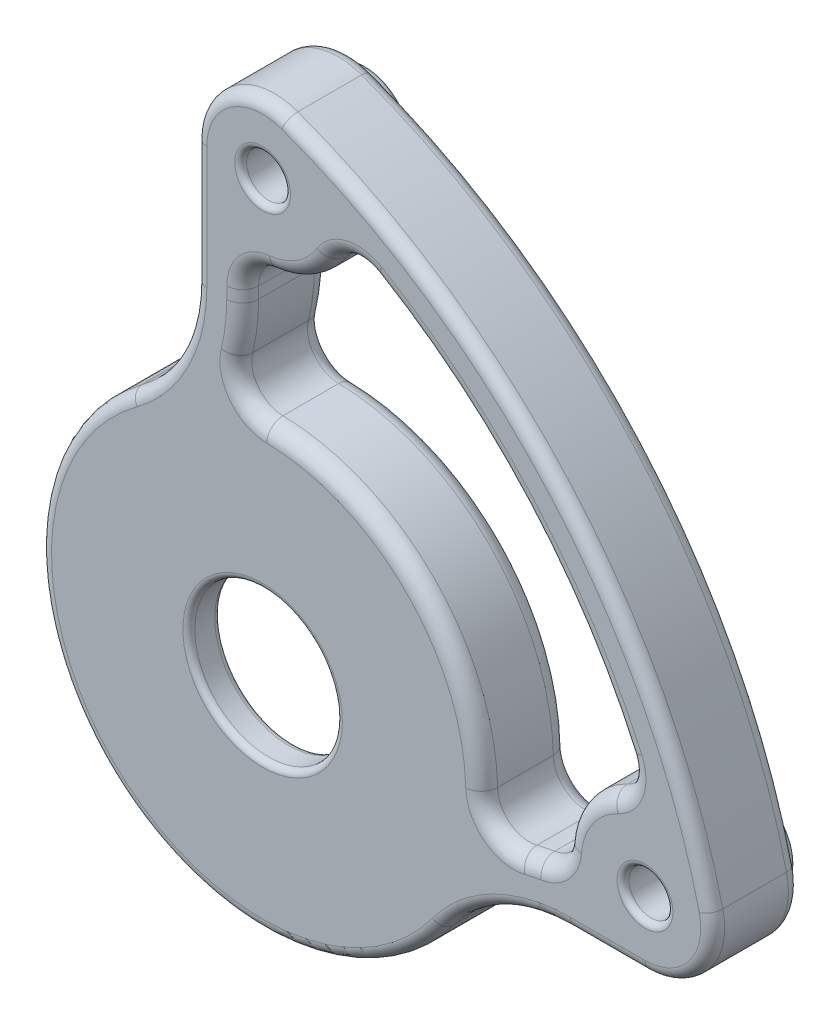
SolidWorks part; units mm, degrees
ref_plane "Front Plane" through (0, 0, 0) normal (0, 0, 1) x (1, 0, 0)
ref_plane "Top Plane" through (0, 0, 0) normal (0, 1, 0) x (1, 0, 0)
ref_plane "Right Plane" through (0, 0, 0) normal (1, 0, 0) x (0, 0, -1)
sketch "Sketch1" plane through (0, 0, 0) normal (0, 0, 1) x (1, 0, 0)
  line L0 (-4.25, 27) -> (-4.25, 19.3116)
  line L1 (24, -4.25) -> (19.3116, -4.25)
  circle A0 centre (0, 0) radius 4.63
  arc A1 (-8.3125, 11.2651) -> (11.2651, -8.3125) centre (0, 0) ccw
  circle A2 centre (0, 27) radius 1.375
  circle A3 centre (24, 0) radius 1.375
  arc A4 (1.4667, 30.9889) -> (-4.25, 27) centre (0, 27) ccw
  arc A5 (24, -4.25) -> (28.1333, 0.9889) centre (24, 0) ccw
  arc A6 (28.1333, 0.9889) -> (1.4667, 30.9889) centre (-13.2001, -8.9001) ccw
  arc A7 (19.3116, -4.25) -> (11.2651, -8.3125) centre (19.3116, -14.25) ccw
  arc A8 (-4.25, 19.3116) -> (-8.3125, 11.2651) centre (-14.25, 19.3116) cw
  dimension "D1" = 9.26
  dimension "D2" = 28
  dimension "D3" = 2.75
  dimension "D6" = 8.5
  dimension "D7" = 8.5
  dimension "D8" = 85
  dimension "D9" = 10
  dimension "D4" = 27
  dimension "D5" = 24
extrude "Boss-Extrude1" add sketch "Sketch1" along normal blind 5.5
sketch "Sketch2" plane through (0, 0, 5.5) normal (0, 0, 1) x (1, 0, 0)
  circle A0 centre (0, 27) radius 3
  circle A1 centre (24, 0) radius 3
  circle A2 centre (24, 0) radius 1.375 construction
  circle A3 centre (0, 27) radius 1.375 construction
  circle A4 centre (24, 0) radius 1.375
  circle A5 centre (0, 27) radius 1.375
  dimension "D1" = 6
extrude "Boss-Extrude2" add sketch "Sketch2" along normal blind 1
sketch "Sketch3" plane through (0, 0, 5.5) normal (0, 0, 1) x (1, 0, 0)
  line L2 (-1.25, 19.3116) -> (-1.25, 27)
  line L3 (-1.25, 19.3116) -> (-1.25, 22.1588)
  line L4 (24, -1.25) -> (19.3116, -1.25)
  circle A0 centre (0, 0) radius 11.75
  arc A3 (19.3116, -1.25) -> (8.8511, -6.5313) centre (19.3116, -14.25) ccw
  arc A4 (25.2157, 0.2909) -> (0.4314, 28.1732) centre (-13.2001, -8.9001) ccw
  arc A5 (23.7752, 4.9949) -> (4.9341, 26.1912) centre (-13.2001, -8.9001) ccw
  arc A6 (19.159, -1.2509) -> (13.4976, -2.6226) centre (19.3116, -14.25) ccw
  arc A7 (-6.5312, 8.8511) -> (-1.25, 19.3116) centre (-14.25, 19.3116) ccw
  arc A8 (-2.6226, 13.4976) -> (-1.25, 19.3116) centre (-14.25, 19.3116) ccw
  circle A10 centre (24, 0) radius 5
  arc A11 (23.7752, 4.9949) -> (19.159, -1.2509) centre (24, 0) ccw
  circle A13 centre (0, 27) radius 5
  arc A14 (-1.25, 22.1588) -> (4.9341, 26.1912) centre (0, 27) ccw
  arc A15 (13.4976, -2.6226) -> (-2.6226, 13.4976) centre (0, 0) ccw
  circle A18 centre (0, 0) radius 13.75 construction
  circle M16 centre (0, 0) radius 4.63
  dimension "D1" = 23.5
  dimension "D2" = 3
  dimension "D3" = 3
  dimension "D4" = 2
  dimension "D5" = 2
  dimension "D6" = 3
  dimension "D7" = 2
extrude "Cut-Extrude1" cut sketch "Sketch3" against normal blind 3.5 contours A0 M16 region at (6.4231, 9.4396, 5.5)
extrude "Cut-Extrude2" cut sketch "Sketch3<3>" against normal through all contours A15 A11 A5 A14 L3 A8 region at (11.2082, 13.0572, 5.5)
sketch "Sketch3<3>" plane through (0, 0, 5.5) normal (0, 0, 1) x (1, 0, 0) same geometry as "Sketch3"
fillet "Fillet1" radius 2 6 edges at (23.7752, 4.9949, 2.75) (4.9341, 26.1912, 2.75) (-1.25, 22.1588, 2.75) (-2.6226, 13.4976, 2.75) (19.159, -1.2509, 2.75) (13.4976, -2.6226, 2.75)
fillet "Fillet2" radius 1 26 edges at (-0.738, 21.3766, 0) (-1.2655, 14.528, 0) (9.7227, 9.7227, 0) (19.9006, 2.8627, 0) (22.9306, 5.6489, 0) (16.3225, 17.3422, 0) (5.4846, 25.2756, 0) (-0.738, 21.3766, 5.5) (-1.2655, 14.528, 5.5) (9.7227, 9.7227, 5.5) (19.9006, 2.8627, 5.5) (22.9306, 5.6489, 5.5) (16.3225, 17.3422, 5.5) (5.4846, 25.2756, 5.5) (2.6705, 22.7729, 0) (2.6705, 22.7729, 5.5) (-1.3435, 17.7556, 0) (-1.3435, 17.7556, 5.5) (-1.25, 19.6759, 0) (-1.25, 19.6759, 5.5) (14.528, -1.2655, 0) (16.773, -1.5003, 0) (18.4871, -0.7887, 0) (14.528, -1.2655, 5.5) (16.773, -1.5003, 5.5) (18.4871, -0.7887, 5.5)
fillet "Fillet3" radius 0.75 16 edges at (27.3366, -2.6325, 0) (21.6558, -4.25, 0) (14.8047, -5.3232, 0) (-9.8995, -9.8995, 0) (-5.3232, 14.8047, 0) (-4.25, 23.1558, 0) (-2.432, 30.4854, 0) (27.3366, -2.6325, 5.5) (21.6558, -4.25, 5.5) (14.8047, -5.3232, 5.5) (-9.8995, -9.8995, 5.5) (-5.3232, 14.8047, 5.5) (-4.25, 23.1558, 5.5) (-2.432, 30.4854, 5.5) (18.5648, 19.3353, 0) (18.5648, 19.3353, 5.5)
chamfer "Chamfer1" distance 0.5 angle 45 2 edges at (25.375, 0, 6.5) (1.375, 27, 6.5)
fillet "Fillet4" radius 0.375 12 edges at (4.63, 0, 0) (1.375, 27, 0) (25.375, 0, 0) (27, 0, 6.5) (27, 0, 5.5) (3, 27, 5.5) (3, 27, 6.5) (4.63, 0, 2) (25.375, 0, 6) (25.875, 0, 6.5) (1.375, 27, 6) (1.875, 27, 6.5)
fillet "Fillet5" radius 0.3125 2 edges at (11.75, 0, 5.5) (11.75, 0, 2)
mirror "Mirror1" about plane through (19.3116, -14.25, 0) normal (0, 0, 1) of bodies 104
delete or keep bodies "Body-Delete/Keep 1" type delete bodies bodies 104
